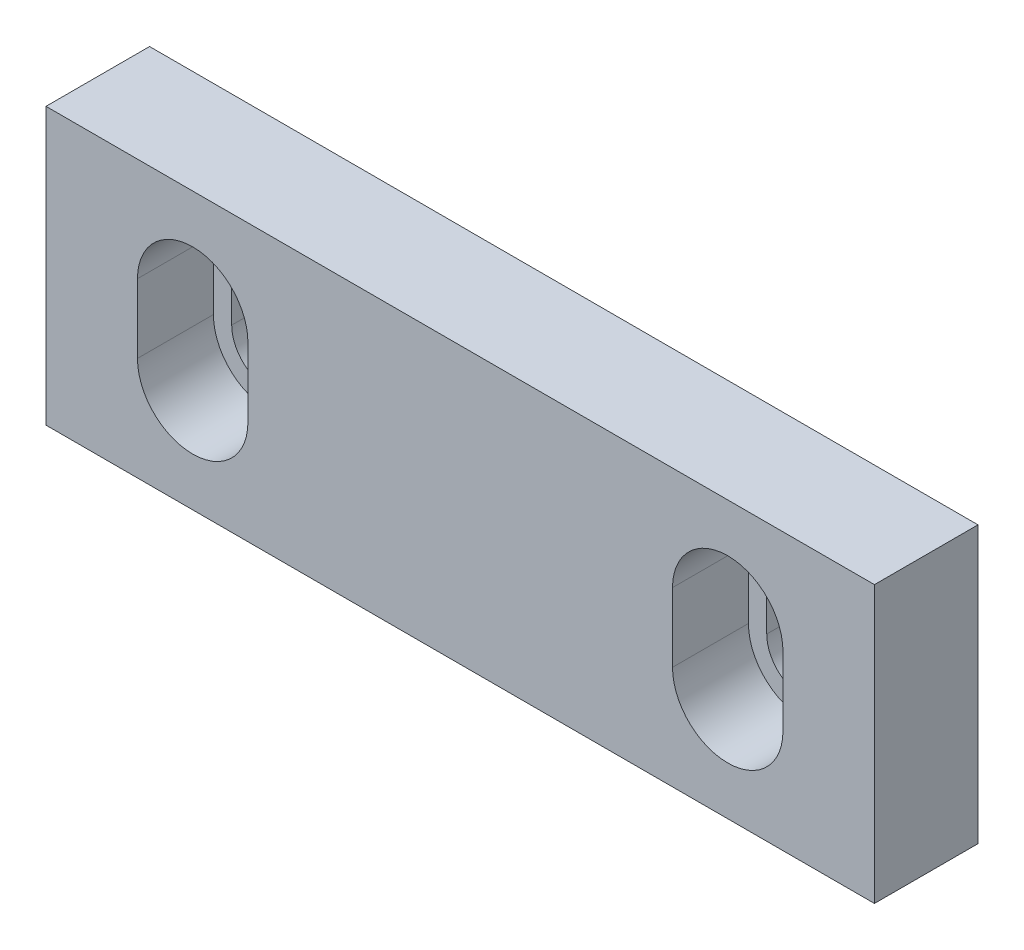
SolidWorks part; units mm, degrees
ref_plane "Front Plane" through (0, 0, 0) normal (0, 0, 1) x (1, 0, 0)
ref_plane "Top Plane" through (0, 0, 0) normal (0, 1, 0) x (1, 0, 0)
ref_plane "Right Plane" through (0, 0, 0) normal (1, 0, 0) x (0, 0, -1)
sketch "Sketch1" plane through (0, 0, 0) normal (0, 0, 1) x (1, 0, 0)
  line L0 (49.2125, 0) -> (-49.2125, 0) construction
  line L1 (76.2, 25.4) -> (-76.2, 25.4)
  line L2 (76.2, 25.4) -> (76.2, -25.4)
  line L3 (76.2, -25.4) -> (-76.2, -25.4)
  line L4 (-76.2, 25.4) -> (-76.2, -25.4)
  line L5 (76.2, 25.4) -> (-76.2, -25.4) construction
  line L6 (76.2, -25.4) -> (-76.2, 25.4) construction
  line L7 (-49.2125, -6.35) -> (-49.2125, 6.35) construction
  line L8 (-59.3725, -6.35) -> (-59.3725, 6.35)
  line L9 (-39.0525, -6.35) -> (-39.0525, 6.35)
  line L10 (49.2125, -6.35) -> (49.2125, 6.35) construction
  line L11 (39.0525, -6.35) -> (39.0525, 6.35)
  line L12 (59.3725, -6.35) -> (59.3725, 6.35)
  line L13 (-56.007, -6.35) -> (-56.007, 6.35)
  line L14 (-42.418, -6.35) -> (-42.418, 6.35)
  line L15 (42.418, -6.35) -> (42.418, 6.35)
  line L16 (56.007, -6.35) -> (56.007, 6.35)
  arc A0 (-59.3725, -6.35) -> (-39.0525, -6.35) centre (-49.2125, -6.35) ccw
  arc A1 (-39.0525, 6.35) -> (-59.3725, 6.35) centre (-49.2125, 6.35) ccw
  arc A2 (39.0525, -6.35) -> (59.3725, -6.35) centre (49.2125, -6.35) ccw
  arc A3 (59.3725, 6.35) -> (39.0525, 6.35) centre (49.2125, 6.35) ccw
  arc A4 (-42.418, 6.35) -> (-56.007, 6.35) centre (-49.2125, 6.35) ccw
  arc A5 (-56.007, -6.35) -> (-42.418, -6.35) centre (-49.2125, -6.35) ccw
  arc A6 (56.007, 6.35) -> (42.418, 6.35) centre (49.2125, 6.35) ccw
  arc A7 (42.418, -6.35) -> (56.007, -6.35) centre (49.2125, -6.35) ccw
  point P0 (0, 0)
  point P9 (0, 0)
  point P11 (-49.2125, 0)
  point P17 (49.2125, 0)
  dimension "D3" = 10.16
  dimension "D1" = 152.4
  dimension "D2" = 50.8
  dimension "D4" = 98.425
  dimension "D5" = 12.7
  dimension "D6" = 13.589
extrude "Boss-Extrude1" add sketch "Sketch1" along normal blind 19.05 contours L1 L4 L3 L2 A3 L12 A2 L11 A1 L9 A0 L8 region at (0, 0, 0)
extrude "Boss-Extrude2" add sketch "Sketch1<3>" along normal blind 5.08 contours L9 A1 L8 A0 A5 L13 A4 L14 | L12 A3 L11 A2 A7 L15 A6 L16 region at (-58.9848, 0, 0) region at (39.4402, 0, 0)
sketch "Sketch1<3>" plane through (0, 0, 0) normal (0, 0, 1) x (1, 0, 0) same geometry as "Sketch1"
